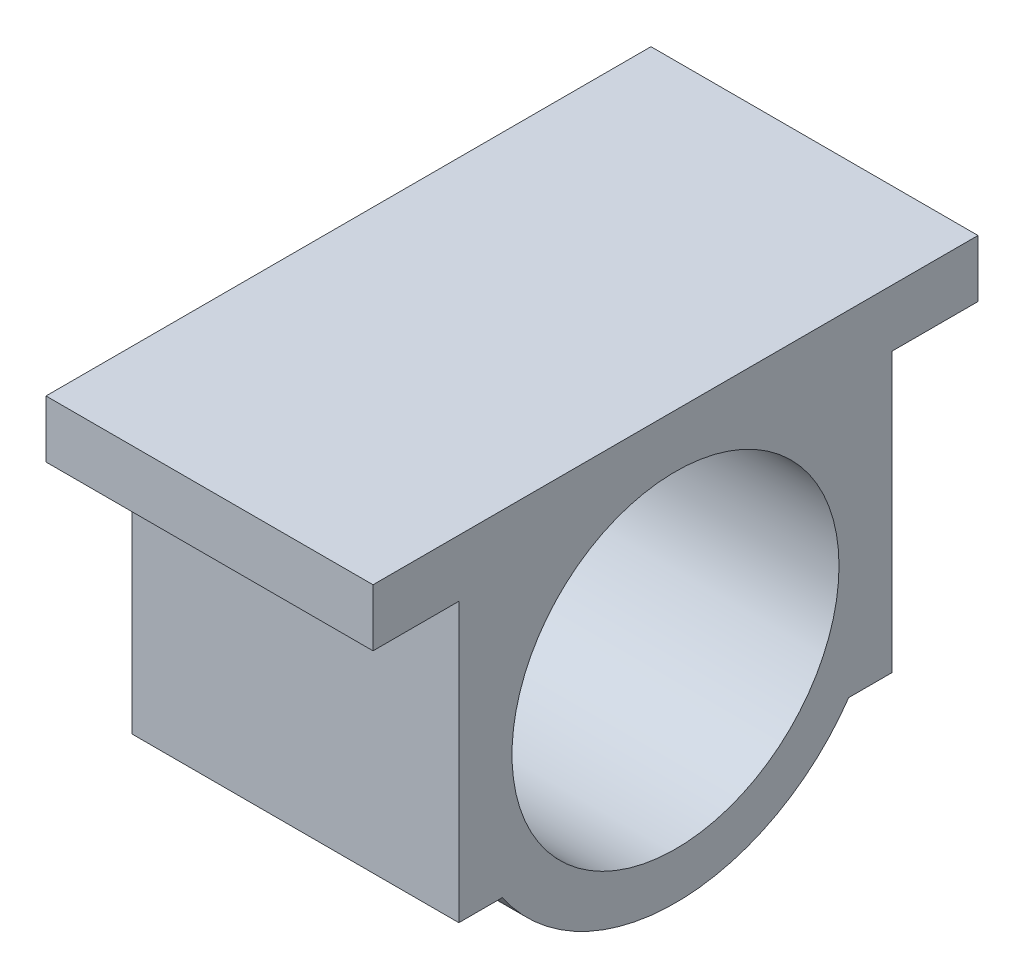
SolidWorks part; units mm, degrees
material "1060 Alloy"
ref_plane "Front Plane" through (0, 0, 0) normal (0, 0, 1) x (1, 0, 0)
ref_plane "Top Plane" through (0, 0, 0) normal (0, 1, 0) x (1, 0, 0)
ref_plane "Right Plane" through (0, 0, 0) normal (1, 0, 0) x (0, 0, -1)
sketch "Sketch1" plane through (0, 0, 0) normal (1, 0, 0) x (0, 0, -1)
  line L0 (0, 122.2832) -> (0, 20.7221) construction
  line L1 (-53, -29.1) -> (-42.3692, -29.1)
  line L2 (-53, -29.1) -> (-53, 39)
  line L3 (-53, 39) -> (-74, 39)
  line L4 (-74, 39) -> (-74, 53)
  line L5 (-74, 53) -> (74, 53)
  line L6 (53, -29.1) -> (42.3692, -29.1)
  line L7 (74, 39) -> (74, 53)
  line L8 (53, 39) -> (74, 39)
  line L9 (53, -29.1) -> (53, 39)
  line L10 (0, -40) -> (0, -51.4) construction
  arc A0 (-42.3692, -29.1) -> (42.3692, -29.1) centre (0, 0) ccw
  circle A1 centre (0, 0) radius 40
  point P13 (0, 53)
  dimension "D5" = 80
  dimension "D6" = 11.4
  dimension "D1" = 148
  dimension "D2" = 14
  dimension "D3" = 21
  dimension "D4" = 68.1
  dimension "D7" = 53
extrude "Boss-Extrude1" add sketch "Sketch1" along normal mid plane 80
sketch "Sketch2" plane through (0, 0, -53) normal (0, 0, -1) x (-1, 0, 0)
  line L0 (-40, -29.1) -> (-40, 39) construction
  line L1 (-40, 0.5) -> (40, 0.5)
  line L2 (-40, 0.5) -> (-40, -2.8)
  line L3 (-40, -2.8) -> (40, -2.8)
  line L4 (40, 0.5) -> (40, -2.8)
  line L5 (40, -29.1) -> (40, 39) construction
  line L7 (-40, -29.1) -> (40, -29.1) construction
  dimension "D1" = 3.3
  dimension "D2" = 26.3
extrude "Cut-Extrude1" [suppressed] cut sketch "Sketch2" against normal blind 19
sketch "Sketch3" plane through (0, -29.1, 0) normal (0, -1, 0) x (1, 0, 0)
  line L0 (22.3, -45.8) -> (22.3, -53) construction
  line L1 (40, -53) -> (-40, -53) construction
  line L2 (22.3, -45.8) -> (40, -45.8) construction
  line L3 (40, -42.3692) -> (40, -53) construction
  circle A0 centre (22.3, -45.8) radius 6.6
  dimension "D1" = 13.2
  dimension "D2" = 7.2
  dimension "D3" = 17.7
extrude "Cut-Extrude2" [suppressed] cut sketch "Sketch3" along normal through all from offset 9.8 offset against normal yes
sketch "Sketch4" [suppressed] plane through (0, -19.3, 0) normal (0, -1, 0) x (1, 0, 0)
  circle A0 centre (22.3, -45.8) radius 4.35
  dimension "D1" = 8.7
extrude "Cut-Extrude3" [suppressed] cut sketch "Sketch4" against normal blind 45.5
pattern_linear "LPattern1" [suppressed] count 3 spacing 25 of bodies 104
other "DeleteFace1" [suppressed]
sketch "Sketch5" plane through (0, 53, 0) normal (0, 1, 0) x (1, 0, 0)
  line L0 (-32, 62.5) -> (-20, 62.5) construction
  line L1 (40, 74) -> (-40, 74) construction
  line L2 (-40, 74) -> (-40, -74) construction
  line L3 (-72.0395, 0) -> (41.5363, 0) construction
  line L4 (0, 89.2861) -> (0, -18.3375) construction
  circle A0 centre (0, 0) radius 4.5
  circle A1 centre (-32, 62.5) radius 2.1
  circle A2 centre (-20, 62.5) radius 3.3
  circle A3 centre (32, 62.5) radius 2.1
  circle A4 centre (20, 62.5) radius 3.3
  circle A5 centre (32, -62.5) radius 2.1
  circle A6 centre (20, -62.5) radius 3.3
  circle A7 centre (-20, -62.5) radius 3.3
  circle A8 centre (-32, -62.5) radius 2.1
  dimension "D1" = 6.6
  dimension "D2" = 4.2
  dimension "D6" = 9
  dimension "D3" = 12
  dimension "D4" = 11.5
  dimension "D5" = 8
extrude "Cut-Extrude4" [suppressed] cut sketch "Sketch5" against normal blind 24.5
chamfer "Chamfer1" [suppressed] distance 1 angle 45
equation "\"M5_tap\"=4.2mm\t\t\t\t\t\t\t' Below you can do mesurements as follows: cm, mm, ft, in, m, "
equation "\"M5_clearence\"=5.5mm"
equation "\"M6_tap\"=5mm"
equation "\"M6_clearence\"=6.6mm"
equation "\"work_area_width\"=1100mm"
equation "\"work_area_depth\"=900mm"
equation "\"steel_base_width\"=3in\t"
equation "\"steel_base_height\"=2in"
equation "\"steel_base_wall_thickness\"=0.125in"
equation "\"steel_base_radius\"=6mm"
equation "\"steel_sides_width\"=3in\t\t\t\t\t'this tube is rotated so flip width/height"
equation "\"steel_sides_height\"=2in\t\t\t\t'this tube is rotated so flip width/height"
equation "\"steel_sides_wall_thickness\"=0.125in"
equation "\"steel_sides_radius\"=6mm"
equation "\"steel_gantry_width\"=4in\t\t\t\t'this tube is rotated so flip width/height"
equation "\"steel_gantry_height\"=3in\t\t\t\t'this tube is rotated so flip width/height"
equation "\"steel_gantry_wall_thickness\"=0.125in"
equation "\"steel_gantry_radius\"=6mm"
equation "\"steel_rollers_width\"=3in"
equation "\"steel_rollers_height\"=2in\t\t\t\t'keep as low as possible as this increases how big plastic parts are"
equation "\"steel_rollers_wall_thickness\"=0.125in"
equation "\"steel_rollers_radius\"=6mm"
equation "\"steel_zbox_width\"=4in\t\t\t\t\t'if the gantry height (rotated) is too thick, a wider zbox is necessary"
equation "\"steel_zbox_height\"=2in\t\t\t\t\t'hole patteren changes as the zbox and gantry height (rotated) changes."
equation "\"steel_zbox_wall_thickness\"=0.125in"
equation "\"steel_zbox_radius\"=6mm"
equation "\"alu_zangle_width\"=3.5in\t\t\t\t\t'check that it doesn't interfer with the gantry"
equation "\"alu_zangle_height\"=2in"
equation "\"alu_zangle_wall_thickness\"=0.375in\t\t\t'check that it doesn't interfer with the gantry"
equation "\"D1@Sketch5\"=\"M6_clearence\""
equation "\"D2@Sketch5\"=\"M5_tap\""
